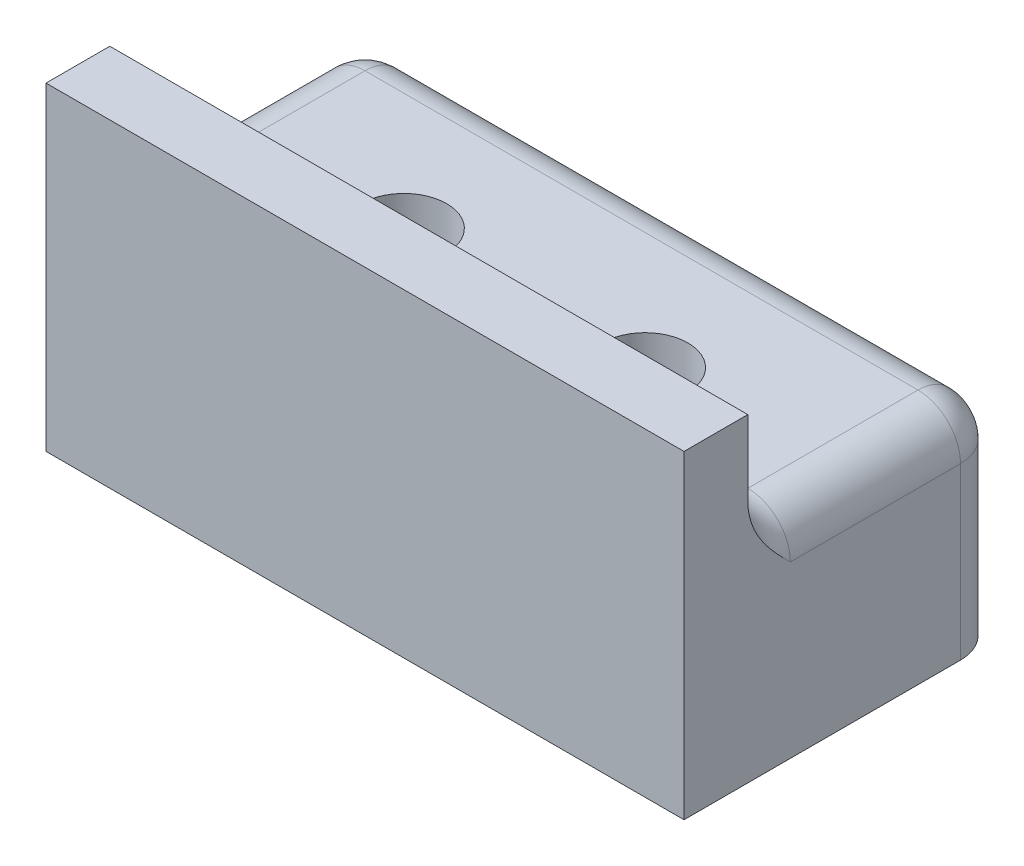
SolidWorks part; units mm, degrees
material "6061-T6 (anodized black)"
ref_plane "Front Plane" through (0, 0, 0) normal (0, 0, 1) x (1, 0, 0)
ref_plane "Top Plane" through (0, 0, 0) normal (0, 1, 0) x (1, 0, 0)
ref_plane "Right Plane" through (0, 0, 0) normal (1, 0, 0) x (0, 0, -1)
sketch "Sketch1" plane through (0, 0, 0) normal (0, 1, 0) x (1, 0, 0)
  line L1 (-19.05, -9.525) -> (19.05, -9.525)
  line L2 (-19.05, -9.525) -> (-19.05, 9.525)
  line L3 (-19.05, 9.525) -> (19.05, 9.525)
  line L4 (19.05, -9.525) -> (19.05, 9.525)
  line L5 (-19.05, -9.525) -> (19.05, 9.525) construction
  line L6 (-19.05, 9.525) -> (19.05, -9.525) construction
  line L7 (7.2009, 9.525) -> (7.2009, -9.525) construction
  line L8 (0, -9.525) -> (0, 9.525) construction
  line L9 (9.7536, 0) -> (19.05, 0) construction
  line L10 (4.6482, 0) -> (-4.6482, 0) construction
  circle A0 centre (7.2009, 0) radius 2.5527
  circle A1 centre (-7.2009, 0) radius 2.5527
  point P0 (0, 0)
  point P6 (0, 0)
  point P11 (0, 0)
  dimension "D4" = 5.1054
  dimension "D1" = 19.05
  dimension "D2" = 38.1
extrude "Boss-Extrude1" add sketch "Sketch1" along normal blind 12.7
sketch "Sketch3" plane through (0, 12.7, 0) normal (0, 1, 0) x (1, 0, 0)
  line L0 (-19.05, 9.525) -> (-19.05, -9.525) construction
  line L1 (-19.05, -5.715) -> (19.05, -5.715)
  line L2 (-19.05, -5.715) -> (-19.05, -9.525)
  line L3 (-19.05, -9.525) -> (19.05, -9.525)
  line L4 (19.05, -5.715) -> (19.05, -9.525)
  line L5 (-19.05, -5.715) -> (19.05, -9.525) construction
  line L6 (-19.05, -9.525) -> (19.05, -5.715) construction
  point P4 (0, -7.62)
  dimension "D1" = 3.81
extrude "Boss-Extrude2" add sketch "Sketch3" along normal blind 6.35
fillet "Fillet1" radius 2.54 5 edges at (19.05, 6.35, -9.525) (-19.05, 6.35, -9.525) (-19.05, 12.7, -1.905) (19.05, 12.7, -1.905) (0, 12.7, -9.525)
fillet "Fillet2" radius 2.54 3 edges at (18.3061, 11.9561, 5.715) (-18.3061, 11.9561, 5.715) (0, 12.7, 5.715)
